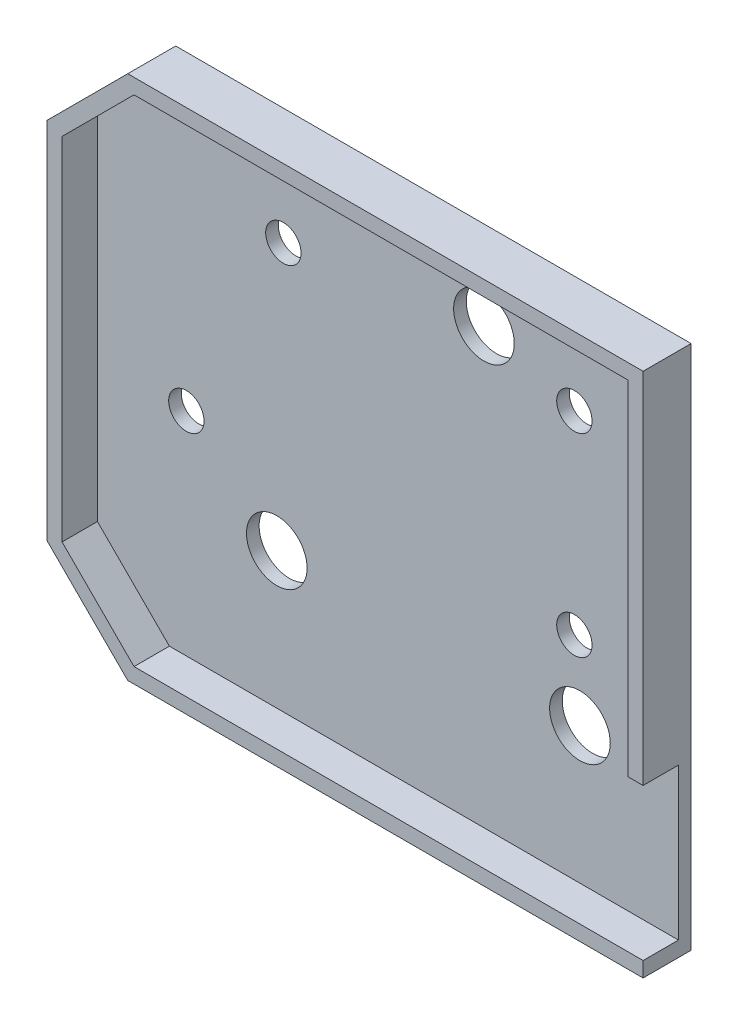
SolidWorks part; units mm, degrees
ref_plane "Plan de face" through (0, 0, 0) normal (0, 0, 1) x (1, 0, 0)
ref_plane "Plan de dessus" through (0, 0, 0) normal (0, 1, 0) x (1, 0, 0)
ref_plane "Plan de droite" through (0, 0, 0) normal (1, 0, 0) x (0, 0, -1)
sketch "Esquisse1" plane through (0, 0, 0) normal (0, 0, 1) x (1, 0, 0)
  line L0 (0, -85) -> (16, -101)
  line L4 (118, 3) -> (118, -101)
  line L5 (16, 3) -> (0, -13)
  line L7 (118, 3) -> (16, 3)
  line L8 (0, -13) -> (0, -85)
  line L9 (16, -101) -> (118, -101)
  dimension "D1" = 104
  dimension "D2" = 118
  dimension "D3" = 16
  dimension "D4" = 16
  dimension "D5" = 16
  dimension "D6" = 16
extrude "Boss.-Extru.1" add sketch "Esquisse1" along normal blind 2.5
sketch "Esquisse2" plane through (0, 0, 2.5) normal (0, 0, 1) x (1, 0, 0)
  line L0 (0, -13) -> (0, -85) construction
  line L1 (3, 0) -> (115, 0) construction
  line L2 (3, 0) -> (3, -98) construction
  line L3 (3, -98) -> (115, -98) construction
  line L4 (115, 0) -> (115, -98) construction
  line L5 (16, -101) -> (118, -101) construction
  line L6 (118, -101) -> (118, 3) construction
  line L7 (118, 3) -> (16, 3) construction
  line L9 (3, -83.7574) -> (17.2426, -98)
  line L10 (0, -85) -> (16, -101) construction
  line L11 (3, -14.2426) -> (17.2426, 0)
  line L12 (16, 3) -> (0, -13) construction
  line L13 (115, 0) -> (17.2426, 0)
  line L14 (3, -14.2426) -> (3, -83.7574)
  line L15 (17.2426, -98) -> (115, -98)
  line L16 (118, 3) -> (118, -101) construction
  line L17 (118, -101) -> (16, -101)
  line L18 (16, -101) -> (0, -85)
  line L19 (0, -85) -> (0, -13)
  line L20 (0, -13) -> (16, 3)
  line L21 (16, 3) -> (118, 3)
  line L30 (118, -2.5) -> (118, 3)
  line L31 (115, -98) -> (118, -98)
  line L32 (118, -98) -> (118, -101)
  line L33 (115, 0) -> (115, -68)
  line L34 (115, -68) -> (118, -68)
  line L35 (118, -68) -> (118, -2.5)
  point P24 (116.5, -98)
  dimension "D1" = 3
  dimension "D2" = 3
  dimension "D3" = 3
  dimension "D4" = 3
  dimension "D5" = 3
  dimension "D6" = 3
  dimension "D7" = 30
extrude "Boss.-Extru.2" add sketch "Esquisse2" along normal blind 7
sketch "Esquisse3" plane through (0, 0, 2.5) normal (0, 0, 1) x (1, 0, 0)
  line L0 (118, -98) -> (17.2426, -98) construction
  line L1 (17.2426, 0) -> (115, 0) construction
  line L2 (115, 0) -> (115, -68) construction
  line L3 (3, -83.7574) -> (3, -14.2426) construction
  circle A0 centre (98.5, -71) radius 6
  circle A1 centre (79.5, -12) radius 6
  circle A2 centre (38.5, -71) radius 6
  circle A3 centre (97.4, -17.6) radius 3.5
  circle A4 centre (39.8, -17.6) radius 3.5
  circle A5 centre (20.6, -56) radius 3.5
  circle A6 centre (97.4, -56) radius 3.5
  point P22 (24.054, -17.0093)
  point P23 (70.4493, -17.6)
  point P24 (27.9779, -17.6)
  point P25 (0, 0)
  point P26 (27.2806, -48.7073)
  point P27 (82.343, -48.7073)
  point P28 (0, 0)
  point P29 (0, 0)
  point P30 (64.9155, -17.6)
  point P31 (86.1893, -17.8105)
  point P32 (0, 0)
  point P33 (0, 0)
  dimension "D1" = 27
  dimension "D7" = 17.6
  dimension "D2" = 27
  dimension "D3" = 12
  dimension "D4" = 16.5
  dimension "D5" = 35.5
  dimension "D6" = 35.5
  dimension "D8" = 17.6
  dimension "D9" = 38.4
  dimension "D10" = 57.6
  dimension "D11" = 76.8
extrude "Enlèv. mat.-Extru.1" cut sketch "Esquisse3" against normal blind 10
